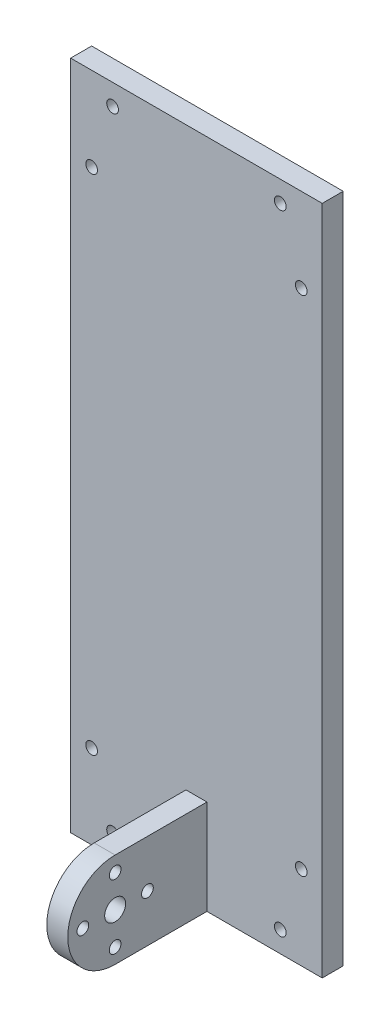
SolidWorks part; units mm, degrees
material "Copper"
ref_plane "Front Plane" through (0, 0, 0) normal (0, 0, 1) x (1, 0, 0)
ref_plane "Top Plane" through (0, 0, 0) normal (0, 1, 0) x (1, 0, 0)
ref_plane "Right Plane" through (0, 0, 0) normal (1, 0, 0) x (0, 0, -1)
sketch "Sketch1" plane through (0, 0, 0) normal (0, 0, 1) x (1, 0, 0)
  line L1 (0, 0) -> (76.2, 0)
  line L2 (0, 0) -> (0, 203.2)
  line L3 (0, 203.2) -> (76.2, 203.2)
  line L4 (76.2, 0) -> (76.2, 203.2)
  dimension "D1" = 76.2
  dimension "D2" = 203.2
extrude "Boss-Extrude1" add sketch "Sketch1" along normal blind 6.35
sketch "Sketch2" plane through (0, 0, 6.35) normal (0, 0, 1) x (1, 0, 0)
  line L0 (76.2, 0) -> (76.2, 203.2) construction
  line L1 (34.925, 28.702) -> (41.275, 28.702)
  line L2 (34.925, 28.702) -> (34.925, 0)
  line L3 (34.925, 0) -> (41.275, 0)
  line L4 (41.275, 28.702) -> (41.275, 0)
  line L5 (0, 203.2) -> (0, 0) construction
  point P6 (76.2, 101.6)
  point P7 (41.275, 14.351)
  point P8 (38.1, 0)
  dimension "D1" = 6.35
  dimension "D2" = 28.702
  dimension "D3" = 87.249
  dimension "D4" = 38.1
extrude "Boss-Extrude2" add sketch "Sketch2" along normal blind 44.45
sketch "Sketch3" plane through (41.275, 0, 0) normal (1, 0, 0) x (0, 0, -1)
  line L0 (-6.35, 0) -> (-6.35, 203.2) construction
  line L1 (-50.8, 0) -> (-6.35, 0) construction
  circle A0 centre (-34.1546, 14.351) radius 3.175
  dimension "D1" = 27.8046
  dimension "D2" = 6.35
  dimension "D3" = 14.351
extrude "Cut-Extrude1" cut sketch "Sketch3" against normal blind 6.35
sketch "Sketch4" plane through (41.275, 0, 0) normal (1, 0, 0) x (0, 0, -1)
  line L0 (-50.8, 0) -> (-6.35, 0) construction
  circle A0 centre (-43.9336, 14.351) radius 1.778
  circle A1 centre (-34.1546, 14.351) radius 3.175 construction
  dimension "D1" = 3.556
  dimension "D2" = 14.351
  dimension "D3" = 9.779
extrude "Cut-Extrude2" cut sketch "Sketch4" against normal blind 6.35
pattern_circular "CirPattern1" count 4 over 360 about axis through (41.275, 14.351, 34.1546) along (1, 0, 0) of "Cut-Extrude2"
sketch "Sketch5" plane through (41.275, 0, 0) normal (1, 0, 0) x (0, 0, -1)
  circle A0 centre (-34.1546, 14.351) radius 14.351
  line M8 (-6.35, 28.702) -> (-50.8, 28.702)
  line M9 (-50.8, 28.702) -> (-50.8, 0)
  line M10 (-50.8, 0) -> (-6.35, 0)
  dimension "D1" = 28.702
extrude "Cut-Extrude3" cut sketch "Sketch5" against normal blind 6.35 contours A0 M8 M9 M10 region at (41.275, 14.351, 48.8374)
sketch "Sketch6" plane through (0, 0, 0) normal (0, 0, -1) x (-1, 0, 0)
  line L0 (0, 0) -> (-76.2, 0) construction
  line L1 (-76.2, 0) -> (-76.2, 203.2) construction
  line L2 (-76.2, 203.2) -> (0, 203.2) construction
  line L3 (0, 203.2) -> (0, 0) construction
  circle A0 centre (-63.5, 6.35) radius 1.778
  circle A1 centre (-12.7, 6.35) radius 1.778
  circle A2 centre (-6.35, 177.8) radius 1.778
  circle A3 centre (-6.35, 25.4) radius 1.778
  circle A4 centre (-69.85, 25.4) radius 1.778
  circle A5 centre (-69.85, 177.8) radius 1.778
  circle A6 centre (-63.5, 196.85) radius 1.778
  circle A7 centre (-12.7, 196.85) radius 1.778
  point P16 (0, 0)
  point P18 (-54.0249, 0)
  dimension "D1" = 3.556
  dimension "D4" = 50.8
  dimension "D5" = 12.7
  dimension "D6" = 6.35
  dimension "D8" = 50.8
  dimension "D9" = 12.7
  dimension "D11" = 6.35
  dimension "D16" = 152.4
  dimension "D17" = 25.4
  dimension "D2" = 6.35
  dimension "D3" = 6.35
  dimension "D7" = 6.35
  dimension "D10" = 6.35
  dimension "D12" = 152.4
  dimension "D13" = 25.4
  dimension "D14" = 6.35
  dimension "D15" = 6.35
extrude "Cut-Extrude4" cut sketch "Sketch6" against normal blind 6.35
